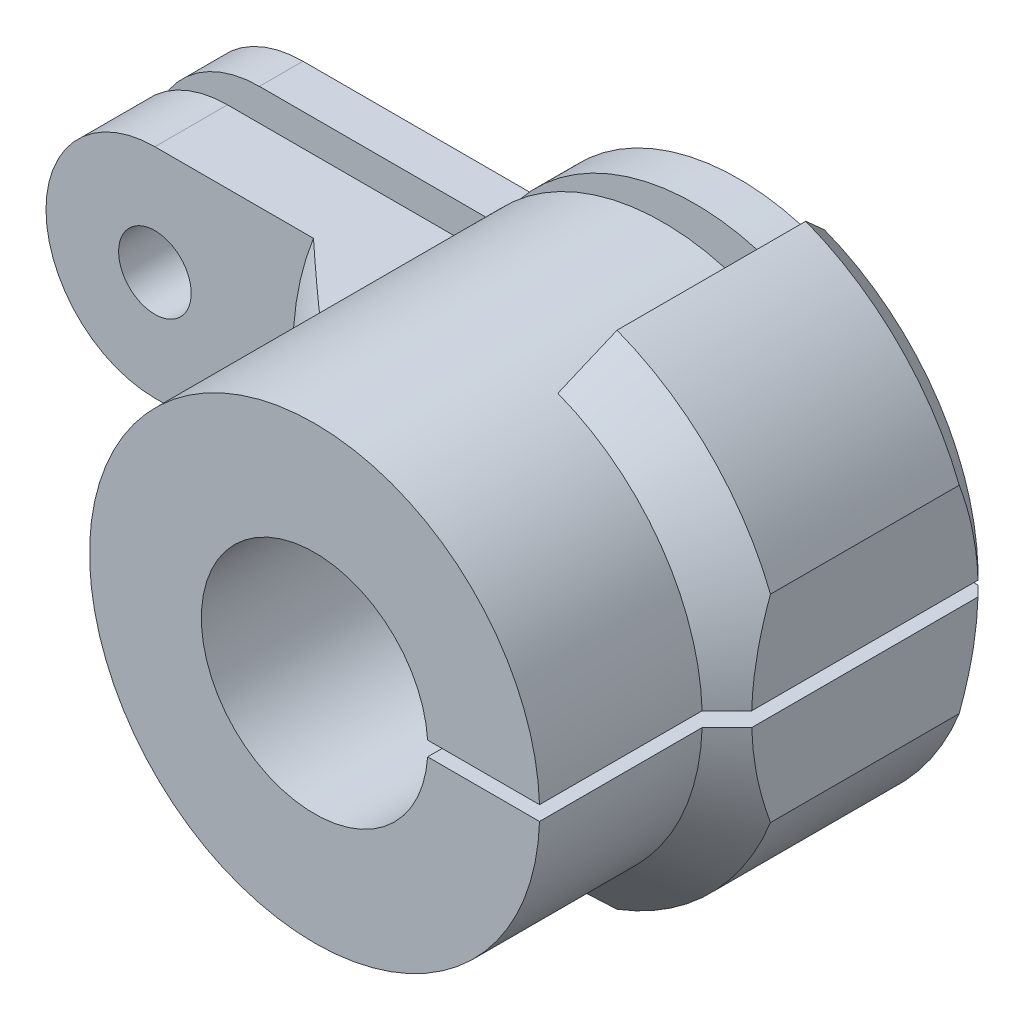
SolidWorks part; units mm, degrees
ref_plane "Front Plane" through (0, 0, 0) normal (0, 0, 1) x (1, 0, 0)
ref_plane "Top Plane" through (0, 0, 0) normal (0, 1, 0) x (1, 0, 0)
ref_plane "Right Plane" through (0, 0, 0) normal (1, 0, 0) x (0, 0, -1)
sketch "Sketch1" plane through (0, 0, 0) normal (0, 0, 1) x (1, 0, 0)
  circle A0 centre (0, 0) radius 7.8
  circle A1 centre (0, 0) radius 15.5
  dimension "D1" = 15.6
  dimension "D2" = 31
extrude "Boss-Extrude1" add sketch "Sketch1" along normal blind 24
sketch "Sketch2" plane through (0, 0, 0) normal (0, 0, -1) x (-1, 0, 0)
  line L0 (30, -7.5) -> (13.5647, -7.5)
  line L1 (30, 7.5) -> (13.5647, 7.5)
  circle A0 centre (30, 0) radius 2.5
  arc A1 (30, -7.5) -> (30, 7.5) centre (30, 0) ccw
  circle A2 centre (0, 0) radius 15.5 construction
  arc A3 (13.5647, 7.5) -> (13.5647, -7.5) centre (0, 0) ccw
  circle A4 centre (0, 0) radius 7.8
  dimension "D1" = 5
  dimension "D2" = 15
  dimension "D3" = 30
extrude "Boss-Extrude2" add sketch "Sketch2" against normal blind 5
ref_plane "Plane1" through (0, 0, -2.2) normal (0, 0, -1) x (-1, 0, 0)
sketch "Sketch4" plane through (0, 0, -2.2) normal (0, 0, -1) x (-1, 0, 0)
  line L2 (13.5647, -7.5) -> (30, -7.5)
  line L3 (30, 7.5) -> (13.5647, 7.5)
  line L4 (13.5647, -7.5) -> (30, -7.5)
  line L5 (30, 7.5) -> (13.5647, 7.5)
  circle A0 centre (30, 0) radius 2.5
  circle A1 centre (30, 0) radius 2.5 construction
  arc A2 (13.5647, 7.5) -> (13.5647, -7.5) centre (0, 0) ccw
  arc A3 (30, -7.5) -> (30, 7.5) centre (30, 0) ccw
  arc A4 (13.5647, 7.5) -> (13.5647, -7.5) centre (0, 0) ccw
  arc A5 (30, -7.5) -> (30, 7.5) centre (30, 0) ccw
  circle A6 centre (0, 0) radius 7.8
  circle A7 centre (0, 0) radius 7.8 construction
  dimension "D1" = 0
extrude "Boss-Extrude3" add sketch "Sketch4" along normal blind 3 separate body
sketch "Sketch5" plane through (0, 0, -5.2) normal (0, 0, -1) x (-1, 0, 0)
  line L0 (0, 0) -> (-10.4177, -18.044) construction
  line L1 (0, 0) -> (-24.1018, 0) construction
  line L2 (0, 0) -> (-5.5547, -14.4705)
  line L5 (-5.5547, -14.4705) -> (-6.6298, -17.2712)
  line L7 (-5.5547, 14.4705) -> (-6.6298, 17.2712)
  line L9 (-15.3092, -2.4247) -> (-18.2722, -2.894) [skipped]
  line L10 (-9.7545, 12.0458) -> (-11.6424, 14.3772) [skipped]
  arc A0 (-6.6298, -17.2712) -> (-11.6424, -14.3772) centre (0, 0) cw
  arc A1 (-5.5547, -14.4705) -> (-9.7545, -12.0458) centre (0, 0) cw
  arc A2 (13.5647, 7.5) -> (13.5647, -7.5) centre (0, 0) ccw construction
  arc A4 (-18.2722, -2.894) -> (-18.2722, 2.894) centre (0, 0) cw
  arc A5 (-9.7545, 12.0458) -> (-5.5547, 14.4705) centre (0, 0) cw
  arc A6 (-11.6424, 14.3772) -> (-6.6298, 17.2712) centre (0, 0) cw
  arc A7 (-9.7545, -12.0458) -> (-5.5547, 14.4705) centre (0, 0) cw
  arc A8 (-11.6424, -14.3772) -> (-11.6424, 14.3772) centre (0, 0) cw
  arc A9 (-15.5, 0) -> (-15.3092, 2.4247) centre (0, 0) cw [skipped]
  point P21 (0, 0)
  dimension "D2" = 3
  dimension "D1" = 60
  dimension "D3" = 3
  dimension "D4" = 9
extrude "Boss-Extrude4" add sketch "Sketch5" against normal blind 15
chamfer "Chamfer1" distance 3 angle 45 1 edges at (15.5, 0, 9.8)
chamfer "Chamfer2" distance 2 angle 45 1 edges at (18.5, 0, -5.2)
chamfer "Chamfer3" distance 5 angle 45 1 edges at (-15.5, 0, 5)
sketch "Sketch6" plane through (0, 0, 24) normal (0, 0, 1) x (1, 0, 0)
  line L0 (0, 0) -> (28.8334, 0)
extrude "Cut-Extrude-Thin1" cut sketch "Sketch6" against normal blind 50 and the other way through all thin thin type mid plane wall 1
ref_plane "Plane2" through (22.2, 0, 0) normal (1, 0, 0) x (0, 0, -1)
sketch "Sketch7" plane through (22.2, 0, 0) normal (1, 0, 0) x (0, 0, -1)
  circle A0 centre (-8.9425, 0) radius 32.9549
extrude "Cut-Extrude1" cut sketch "Sketch7" against normal blind 5
